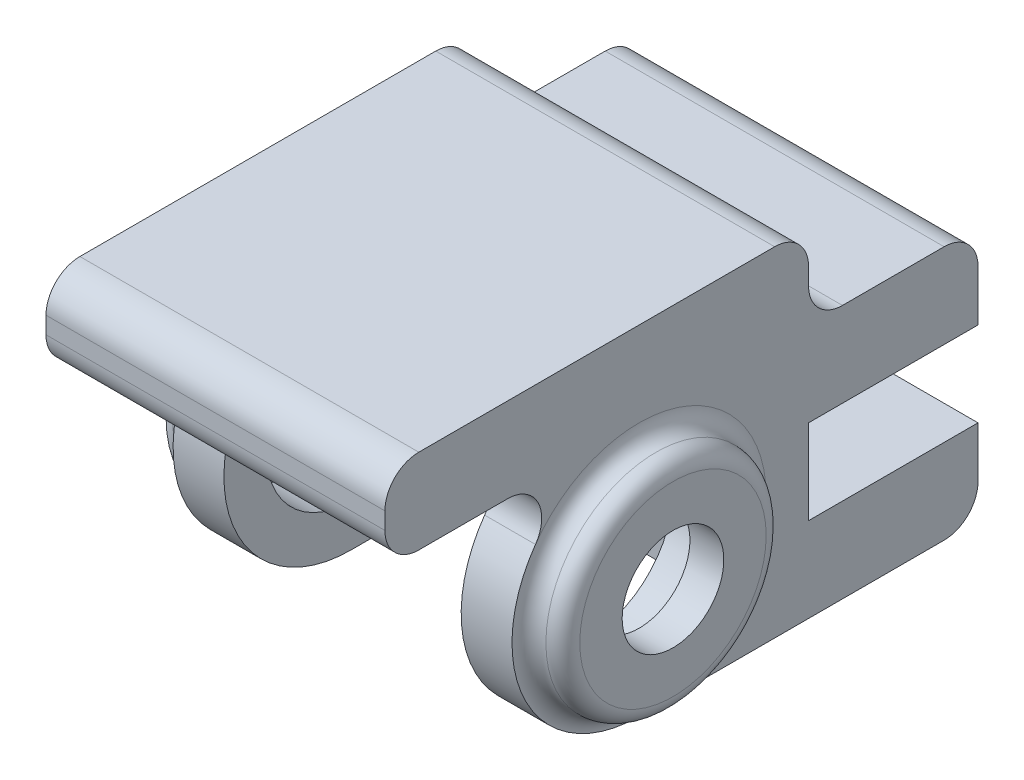
SolidWorks part; units mm, degrees
ref_plane "前视基准面" through (0, 0, 0) normal (0, 0, 1) x (1, 0, 0)
ref_plane "上视基准面" through (0, 0, 0) normal (0, 1, 0) x (1, 0, 0)
ref_plane "右视基准面" through (0, 0, 0) normal (1, 0, 0) x (0, 0, -1)
sketch "草图1" plane through (0, 0, 0) normal (1, 0, 0) x (0, 0, -1)
  line L0 (-63.6094, 0) -> (63.6094, 0) construction
  line L1 (0, 32.8205) -> (0, -32.8205) construction
  line L2 (20, 7.5) -> (0, 7.5)
  line L4 (0, -7.5) -> (20, -7.5)
  line L5 (20, -7.5) -> (20, -2.5)
  line L6 (20, -2.5) -> (10, -2.5)
  line L7 (10, -2.5) -> (10, 2.5)
  line L8 (10, 2.5) -> (20, 2.5)
  line L9 (20, 2.5) -> (20, 7.5)
  arc A0 (0, 7.5) -> (0, -7.5) centre (0, 0) ccw
  circle A1 centre (0, 0) radius 5
  point P4 (0, 0)
  point P8 (0, 0)
  dimension "D5" = 7.5
  dimension "D6" = 10
  dimension "D1" = 5
  dimension "D2" = 10
  dimension "D3" = 5
  dimension "D4" = 20
extrude "凸台-拉伸1" add sketch "草图1" along normal mid plane 20
sketch "草图2" plane through (0, 0, 0) normal (0, 1, 0) x (1, 0, 0)
  line L1 (-7, 8.5) -> (7, 8.5)
  line L2 (-7, 8.5) -> (-7, -7.5)
  line L3 (-7, -7.5) -> (7, -7.5)
  line L4 (7, 8.5) -> (7, -7.5)
  line L7 (-10, -7.5) -> (10, -7.5) construction
  line L8 (10, -7.5) -> (10, 0) construction
  dimension "D1" = 14
  dimension "D2" = 3
  dimension "D3" = 16
extrude "切除-拉伸1" cut sketch "草图2" against normal through all both and the other way through all
sketch "草图3" plane through (0, 7.5, 0) normal (0, 1, 0) x (1, 0, 0)
  line L0 (-10, 20) -> (10, 20)
  line L1 (-10, 20) -> (-10, 0) construction
  line L2 (10, 20) -> (-10, 20) construction
  line L3 (10, 20) -> (10, -15)
  line L4 (10, -15) -> (-10, -15)
  line L5 (-10, -15) -> (-10, 20)
  dimension "D1" = 35
extrude "凸台-拉伸2" add sketch "草图3" along normal blind 5
fillet "圆角3" radius 2 5 edges at (-8.5, 7.5, 0) (8.5, 7.5, 0) (0, -7.5, -20) (0, 7.5, 15) (0, 12.5, 15)
sketch "草图4" plane through (0, 12.5, 0) normal (0, 1, 0) x (1, 0, 0)
  line L0 (10, 20) -> (-10, 20)
  line L1 (10, -13) -> (10, 20) construction
  line L2 (10, 20) -> (-10, 20) construction
  line L3 (-10, 20) -> (-10, -13) construction
  line L4 (-10, 20) -> (-10, 10)
  line L5 (-10, 10) -> (10, 10)
  line L6 (10, 10) -> (10, 20)
  dimension "D1" = 10
extrude "切除-拉伸2" cut sketch "草图4" against normal blind 5
fillet "圆角4" radius 2 3 edges at (0, 12.5, -10) (0, 7.5, -20) (0, 7.5, -10)
fillet "圆角5" radius 5 1 edges at (0, 7.5, -8.5)
sketch "草图5" plane through (-10, 0, 0) normal (-1, 0, 0) x (0, 0, 1)
  circle A0 centre (0, 0) radius 6.5
  circle A1 centre (0, 0) radius 3
  dimension "D1" = 13
  dimension "D2" = 6
extrude "凸台-拉伸3" add sketch "草图5" along normal blind 2
fillet "圆角6" radius 1 2 edges at (-12, 0, 6.5) (-10, 0, -6.5)
mirror "镜向1" about plane through (0, 0, 0) normal (1, 0, 0) of "凸台-拉伸3"
fillet "圆角7" radius 1 2 edges at (10, 0, -6.5) (12, 0, 6.5)
